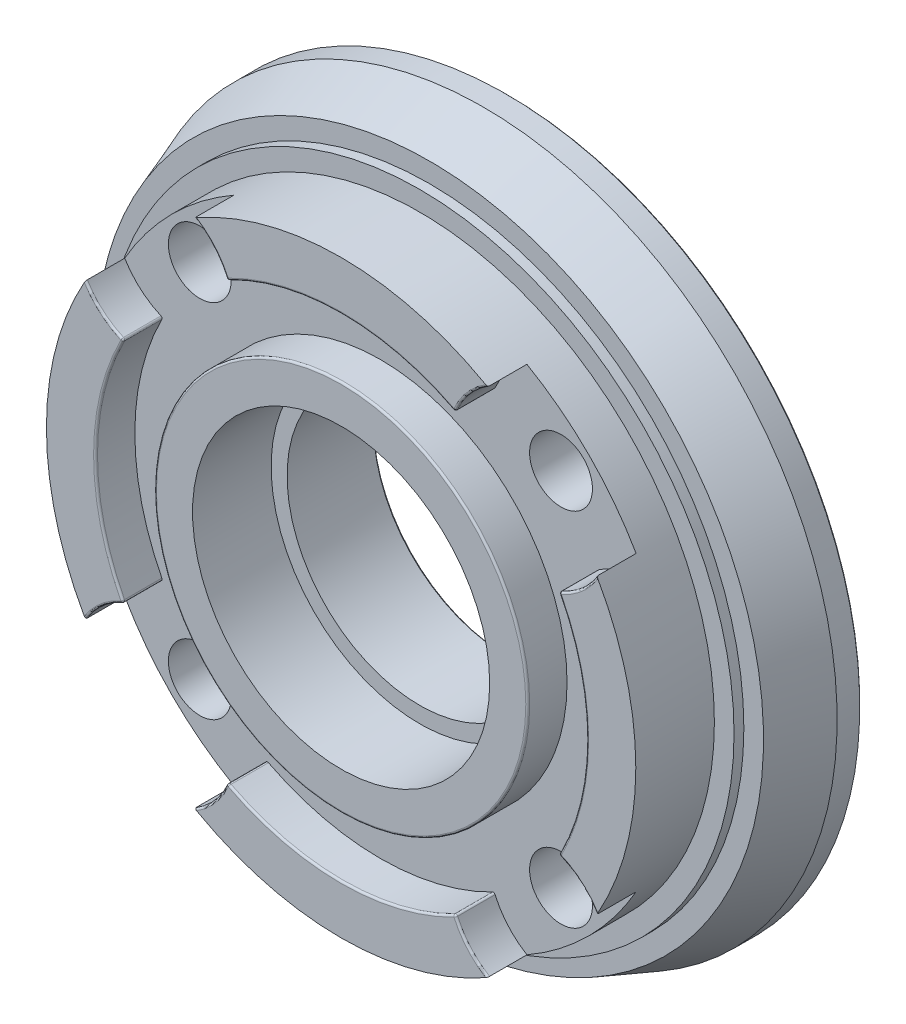
SolidWorks part; units mm, degrees
ref_plane "Front Plane" through (0, 0, 0) normal (0, 0, 1) x (1, 0, 0)
ref_plane "Top Plane" through (0, 0, 0) normal (0, 1, 0) x (1, 0, 0)
ref_plane "Right Plane" through (0, 0, 0) normal (1, 0, 0) x (0, 0, -1)
sketch "Sketch1" plane through (0, 0, 0) normal (0, 0, 1) x (1, 0, 0)
  line L0 (0, 0) -> (13.5, 0) construction
  line L1 (0, 0) -> (9.5459, 9.5459) construction
  circle A0 centre (0, 0) radius 9.5
  circle A1 centre (0, 0) radius 15
  arc A2 (-6.285, 11.9478) -> (-11.9478, 6.285) centre (0, 0) ccw construction
  arc A3 (7.4565, 13.0154) -> (5.7957, 11.0752) centre (9.5459, 9.5459) ccw
  arc A4 (13.0154, -7.4565) -> (11.0752, -5.7957) centre (9.5459, -9.5459) ccw
  arc A5 (-7.4565, -13.0154) -> (-5.7957, -11.0752) centre (-9.5459, -9.5459) ccw
  arc A6 (-13.0154, 7.4565) -> (-11.0752, 5.7957) centre (-9.5459, 9.5459) ccw
  arc A7 (-11.0752, 5.7957) -> (-11.0752, -5.7957) centre (0, 0) ccw
  arc A8 (11.9478, 6.285) -> (6.285, 11.9478) centre (0, 0) ccw construction
  arc A9 (6.285, -11.9478) -> (11.9478, -6.285) centre (0, 0) ccw construction
  arc A10 (-11.9478, -6.285) -> (-6.285, -11.9478) centre (0, 0) ccw construction
  arc A11 (5.7957, 11.0752) -> (-5.7957, 11.0752) centre (0, 0) ccw
  arc A12 (-5.7957, -11.0752) -> (5.7957, -11.0752) centre (0, 0) ccw
  arc A13 (11.0752, -5.7957) -> (11.0752, 5.7957) centre (0, 0) ccw
  arc A14 (-5.7957, 11.0752) -> (-7.4565, 13.0154) centre (-9.5459, 9.5459) ccw
  arc A15 (11.0752, 5.7957) -> (13.0154, 7.4565) centre (9.5459, 9.5459) ccw
  arc A16 (5.7957, -11.0752) -> (7.4565, -13.0154) centre (9.5459, -9.5459) ccw
  arc A17 (-11.0752, -5.7957) -> (-13.0154, -7.4565) centre (-9.5459, -9.5459) ccw
  circle A18 centre (0, 0) radius 7.5625
  point P17 (0, 0)
  dimension "D1" = 19
  dimension "D2" = 30
  dimension "D3" = 27
  dimension "D4" = 45
  dimension "D5" = 8.1
  dimension "D6" = 4
  dimension "D7" = 25
  dimension "D8" = 15.125
extrude "Boss-Extrude1" add sketch "Sketch1" along normal blind 2 contours A14 A11 A3 A1 | A15 A13 A4 A1 | A16 A12 A5 A1 | A17 A7 A6 A1 | A0 A18 region at (-9.2313, 0, 0) region at (13.2504, 0, 0) region at (0, 13.2504, 0) region at (0, -13.2504, 0) region at (-13.2504, 0, 0)
sketch "Sketch2" plane through (0, 0, 0) normal (0, 0, 1) x (1, 0, 0)
  circle A0 centre (0, 0) radius 15
extrude "Boss-Extrude2" add sketch "Sketch2" against normal blind 2
fillet "Fillet1" radius 0.1 8 edges at (-5.7957, -11.0752, 1) (5.7957, -11.0752, 1) (11.0752, -5.7957, 1) (11.0752, 5.7957, 1) (5.7957, 11.0752, 1) (-5.7957, 11.0752, 1) (-11.0752, 5.7957, 1) (-11.0752, -5.7957, 1)
fillet "Fillet2" radius 0.1 21 edges at (6.5042, 12.2199, 2) (5.7793, 11.1194, 2) (-6.5042, 12.2199, 2) (-5.7793, 11.1194, 2) (12.2199, -6.5042, 2) (11.1194, -5.7793, 2) (12.2199, 6.5042, 2) (11.1194, 5.7793, 2) (-6.5042, -12.2199, 2) (-5.7793, -11.1194, 2) (6.5042, -12.2199, 2) (5.7793, -11.1194, 2) (-12.2199, 6.5042, 2) (-11.1194, 5.7793, 2) (-12.2199, -6.5042, 2) (-11.1194, -5.7793, 2) (0, 12.5, 2) (12.5, 0, 2) (0, -12.5, 2) (9.5, 0, 2) (-12.5, 0, 2)
sketch "Sketch3" plane through (0, 0, -2) normal (0, 0, -1) x (-1, 0, 0)
  line L1 (9.1924, 9.1924) -> (-9.1924, 9.1924) construction
  line L2 (-9.1924, 9.1924) -> (-9.1924, -9.1924) construction
  line L3 (-9.1924, -9.1924) -> (9.1924, -9.1924) construction
  line L4 (9.1924, -9.1924) -> (9.1924, 9.1924) construction
  circle A0 centre (0, 0) radius 13 construction
  circle A1 centre (-9.1924, 9.1924) radius 1.6
  circle A2 centre (9.1924, 9.1924) radius 1.6
  circle A3 centre (9.1924, -9.1924) radius 1.6
  circle A4 centre (-9.1924, -9.1924) radius 1.6
  point P17 (0, 0)
  dimension "D1" = 26
  dimension "D2" = 3.2
  dimension "D3" = 4
sketch "Sketch4" plane through (0, 0, -2) normal (0, 0, -1) x (-1, 0, 0)
  circle A0 centre (0, 0) radius 16
  dimension "D1" = 32
extrude "Boss-Extrude3" add sketch "Sketch4" along normal blind 0.5
sketch "Sketch5" plane through (0, 0, -2.5) normal (0, 0, -1) x (-1, 0, 0)
  circle A0 centre (0, 0) radius 18
  dimension "D1" = 36
extrude "Boss-Extrude4" add sketch "Sketch5" along normal blind 4
extrude "Cut-Extrude2" cut sketch "Sketch3" against normal through all and the other way through all
sketch "Sketch6" plane through (0, 0, -6.5) normal (0, 0, -1) x (-1, 0, 0)
  circle A0 centre (-9.1924, 9.1924) radius 2.35
  circle A1 centre (9.1924, 9.1924) radius 2.35
  circle A2 centre (9.1924, -9.1924) radius 2.35
  circle A3 centre (-9.1924, -9.1924) radius 2.35
  point P12 (0, 0)
  dimension "D1" = 4.7
  dimension "D2" = 4
extrude "Cut-Extrude3" cut sketch "Sketch6" against normal blind 4
sketch "Sketch7" plane through (0, 0, -6.5) normal (0, 0, -1) x (-1, 0, 0)
  line L0 (0, 0) -> (0, 13) construction
  line L1 (0, 13) -> (-13, 0) construction
  line L2 (-13, 0) -> (0, -13) construction
  line L3 (0, -13) -> (13, 0) construction
  line L4 (13, 0) -> (0, 13) construction
  circle A0 centre (0, 0) radius 13 construction
  circle A1 centre (0, 13) radius 2.35
  circle A2 centre (13, 0) radius 2.35
  circle A3 centre (0, -13) radius 2.35
  circle A4 centre (-13, 0) radius 2.35
  point P17 (0, 0)
  dimension "D1" = 26
  dimension "D2" = 4.7
  dimension "D3" = 4
extrude "Cut-Extrude4" cut sketch "Sketch7" against normal blind 4
sketch "Sketch8" plane through (0, 0, 0) normal (0, 0, 1) x (1, 0, 0)
  circle A0 centre (0, 0) radius 6.75
  dimension "D1" = 13.5
extrude "Middle Cutout" cut sketch "Sketch8" against normal blind 7
chamfer "Chamfer1" distance 0.1 angle 45 2 edges at (-6.75, 0, -6.5) (-18, 0, -6.5)
sketch "Sketch9" plane through (0, 0, 0) normal (0, 0, 1) x (1, 0, 0)
  circle A0 centre (0, 0) radius 7.5625
  dimension "D1" = 15.125
extrude "Cut-Extrude6" cut sketch "Sketch9" against normal blind 2
chamfer "Chamfer2" distance 1 angle 70 1 edges at (-18, 0, -2.5) first distance on face at (-16, 0, -2.5)
